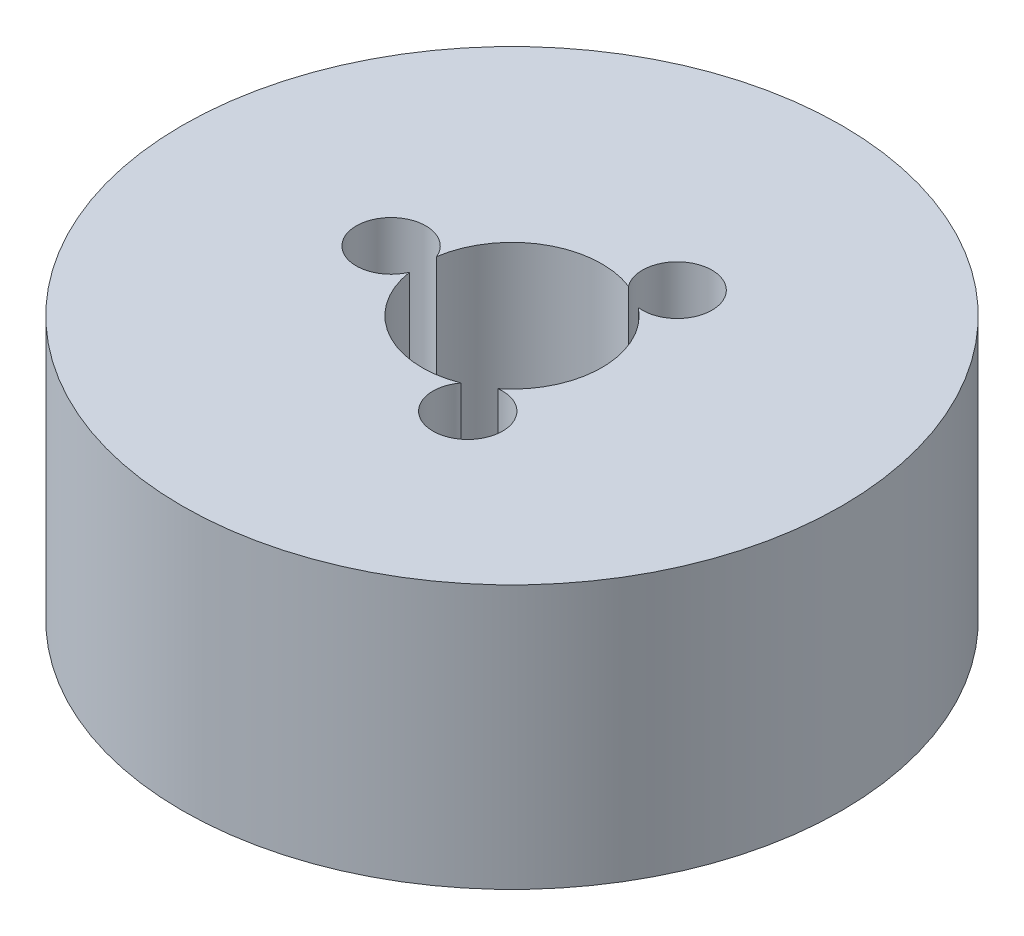
SolidWorks part; units mm, degrees
ref_plane "Front Plane" through (0, 0, 0) normal (0, 0, 1) x (1, 0, 0)
ref_plane "Top Plane" through (0, 0, 0) normal (0, 1, 0) x (1, 0, 0)
ref_plane "Right Plane" through (0, 0, 0) normal (1, 0, 0) x (0, 0, -1)
sketch "Sketch1" plane through (0, 0, 0) normal (0, 1, 0) x (1, 0, 0)
  circle A0 centre (0, 0) radius 27.5
  dimension "FLANGE_OD" = 55
extrude "Boss-Extrude1" add sketch "Sketch1" along normal blind 22
sketch "Sketch2" plane through (0, 0, 0) normal (0, 1, 0) x (1, 0, 0)
  circle A0 centre (0, 0) radius 7.5
  dimension "BORE_D" = 15
extrude "Cut-Extrude1" cut sketch "Sketch2" along normal through all
sketch "Sketch3" plane through (0, 22, 0) normal (0, 1, 0) x (1, 0, 0)
  circle A0 centre (0, 0) radius 10.0863 construction
  circle A1 centre (-10.0863, 0) radius 2.9012
  dimension "BOLT_D" = 5.8023
  dimension "BOLT_PCD" = 20.1726
extrude "Cut-Extrude2" cut sketch "Sketch3" against normal blind 13.9318
pattern_circular "CirPattern1" count 3 over 360 about axis through (0, 0, 0) along (0, 1, 0) of "Cut-Extrude2"
